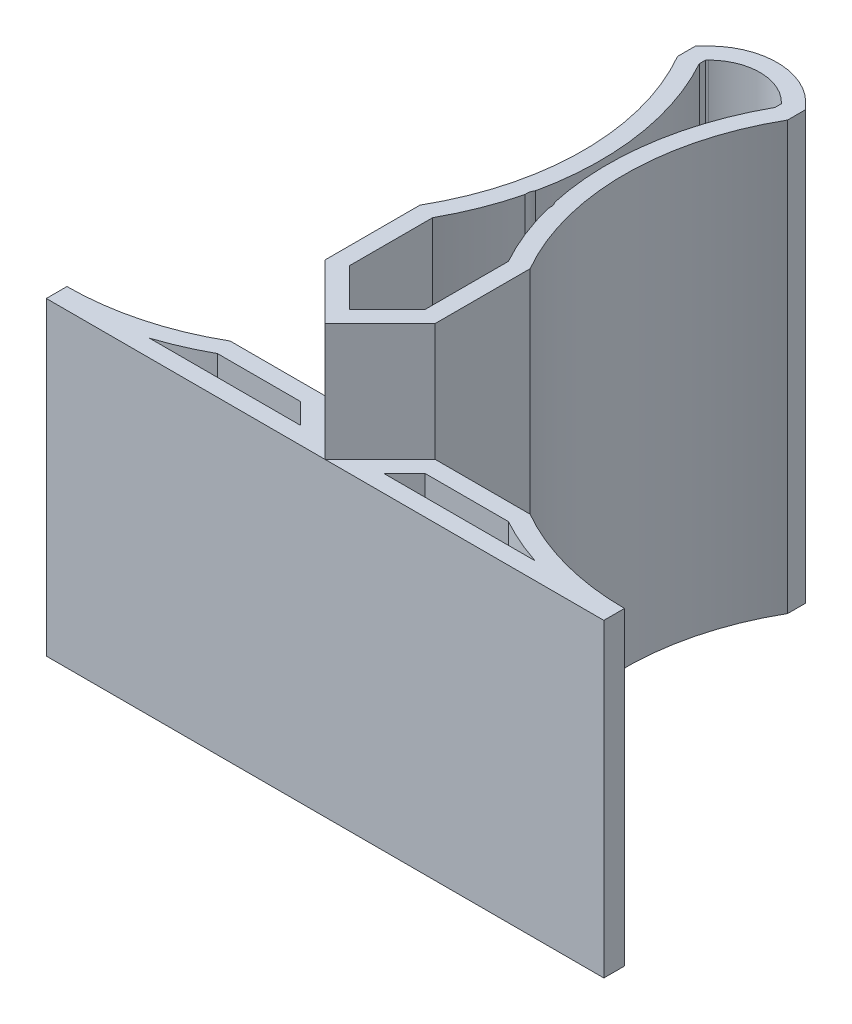
SolidWorks part; units mm, degrees
ref_plane "Front Plane" through (0, 0, 0) normal (0, 0, 1) x (1, 0, 0)
ref_plane "Top Plane" through (0, 0, 0) normal (0, 1, 0) x (1, 0, 0)
ref_plane "Right Plane" through (0, 0, 0) normal (1, 0, 0) x (0, 0, -1)
sketch "Sketch1" plane through (0, 0, 0) normal (0, 1, 0) x (1, 0, 0)
  line L0 (23.7595, 41.275) -> (41.275, 41.275) construction
  line L1 (-41.275, -41.275) -> (-23.7595, -41.275) construction
  line L2 (-41.275, -41.275) -> (-41.275, -23.7595) construction
  line L3 (-41.275, 41.275) -> (-23.7595, 41.275) construction
  line L4 (41.275, -41.275) -> (41.275, -23.7595) construction
  line L5 (-41.275, -41.275) -> (41.275, 41.275) construction
  line L6 (-41.275, 41.275) -> (41.275, -41.275) construction
  line L7 (41.275, 23.7595) -> (41.275, 41.275) construction
  line L8 (-41.275, 23.7595) -> (-41.275, 41.275) construction
  line L9 (23.7595, -41.275) -> (41.275, -41.275) construction
  line L10 (24.7569, 45.085) -> (45.085, 45.085) construction
  line L11 (45.085, 24.7569) -> (45.085, 45.085) construction
  line L12 (45.085, -45.085) -> (45.085, -24.7569) construction
  line L13 (24.7569, -45.085) -> (45.085, -45.085) construction
  line L14 (-45.085, -45.085) -> (-24.7569, -45.085) construction
  line L15 (-45.085, -45.085) -> (-45.085, -24.7569) construction
  line L16 (-45.085, 24.7569) -> (-45.085, 45.085) construction
  line L17 (-45.085, 45.085) -> (-24.7569, 45.085) construction
  line L19 (-51.435, -51.435) -> (51.435, -51.435) construction
  line L20 (-51.435, -51.435) -> (-51.435, 51.435) construction
  line L21 (-51.435, 51.435) -> (51.435, 51.435) construction
  line L22 (51.435, -51.435) -> (51.435, 51.435) construction
  line L23 (-51.435, -51.435) -> (51.435, 51.435) construction
  line L24 (-51.435, 51.435) -> (51.435, -51.435) construction
  arc A1 (-41.275, 23.7595) -> (-41.275, -23.7595) centre (0, 0) ccw construction
  arc A2 (23.7595, 41.275) -> (-23.7595, 41.275) centre (0, 0) ccw construction
  arc A3 (-23.7595, -41.275) -> (23.7595, -41.275) centre (0, 0) ccw construction
  arc A4 (41.275, -23.7595) -> (41.275, 23.7595) centre (0, 0) ccw construction
  arc A5 (45.085, -24.7569) -> (45.085, 24.7569) centre (0, 0) ccw construction
  arc A6 (-24.7569, -45.085) -> (24.7569, -45.085) centre (0, 0) ccw construction
  arc A7 (-45.085, 24.7569) -> (-45.085, -24.7569) centre (0, 0) ccw construction
  arc A8 (24.7569, 45.085) -> (-24.7569, 45.085) centre (0, 0) ccw construction
  point P0 (0, 0)
  dimension "D1" = 82.55
  dimension "D2" = 82.55
  dimension "D3" = 95.25
  dimension "D4" = 3.81
sketch "Sketch2" plane through (0, 0, 0) normal (0, 0, 1) x (1, 0, 0)
  line L0 (0, 48) -> (0, 0) construction
  line L1 (0, 0) -> (0, -9.15) construction
  line L2 (0, 48) -> (0, 69.717) construction
  dimension "Cage height" = 48
  dimension "Plate height" = 21.717
  dimension "D1" = 57.15
  dimension "D2" = 9.15
sketch "Sketch13" plane through (0, 0, 0) normal (0, 1, 0) x (1, 0, 0)
  line L0 (-51.435, -51.435) -> (51.435, -51.435) construction
  line L1 (-41.275, -41.275) -> (-23.7595, -41.275) construction
  line L2 (-41.275, -41.275) -> (-41.275, -23.7595) construction
  line L4 (-51.435, -51.435) -> (0, -51.435)
  line L5 (-41.275, -41.275) -> (-23.7595, -41.275)
  line L6 (-41.275, -41.275) -> (-41.275, -23.7595)
  line L9 (0, -47.625) -> (0, -51.435)
  line L10 (-51.435, 51.435) -> (51.435, -51.435) construction
  line L11 (-41.275, 23.7595) -> (-41.275, 41.275) construction
  line L12 (-51.435, -51.435) -> (-51.435, 51.435) construction
  line L13 (-51.435, 51.435) -> (-41.275, 41.275)
  line L14 (-41.275, 23.7595) -> (-41.275, 41.275)
  line L15 (-51.435, -51.435) -> (-51.435, 51.435)
  arc A0 (-23.7595, -41.275) -> (23.7595, -41.275) centre (0, 0) ccw construction
  arc A2 (-23.7595, -41.275) -> (0, -47.625) centre (0, 0) ccw
  arc A4 (-41.275, 23.7595) -> (-41.275, -23.7595) centre (0, 0) ccw construction
  arc A5 (-41.275, 23.7595) -> (-41.275, -23.7595) centre (0, 0) ccw
extrude "Boss-Extrude2" add sketch "Sketch13" along normal up to vertex (69.717 mm away) and the other way up to vertex (9.15 mm away) up to point (0, 69.717, 0) other way up to point (0, -9.15, 0)
sketch "Sketch15" plane through (0, 69.717, 0) normal (0, 1, 0) x (1, 0, 0)
  line L0 (0, 0) -> (-51.435, -51.435)
  line L1 (-51.435, -51.435) -> (0, -51.435)
  line L2 (0, -51.435) -> (0, 0)
  line L3 (-51.435, -51.435) -> (51.435, -51.435) construction
extrude "Cut-Extrude2" cut sketch "Sketch15" against normal up to vertex (21.717 mm away) up to point (0, 48, 0)
mirror "Mirror1" about plane through (-51.435, 69.717, 51.435) normal (1, 0, 0) of "Boss-Extrude2", "Cut-Extrude2"
sketch "Sketch16" plane through (0, -9.15, 0) normal (0, -1, 0) x (1, 0, 0)
  line L0 (-51.435, 51.435) -> (-51.435, -51.435) construction
  line L1 (-102.87, 51.435) -> (0, 51.435) construction
  line L2 (-51.435, 51.435) -> (-51.435, -51.435) construction
  circle A0 centre (-70.485, 46.355) radius 1.85
  circle A1 centre (-51.435, 25.4) radius 1.85
  circle A3 centre (-32.385, 46.355) radius 1.85
  circle A5 centre (-51.435, -25.4) radius 1.85
  dimension "D1" = 3.7
  dimension "D2" = 19.05
  dimension "D3" = 5.08
  dimension "D4" = 25.4
  dimension "D6" = 25.4
extrude "Cut-Extrude3" cut sketch "Sketch16" against normal blind 31.75
sketch "Sketch17" plane through (0, 69.717, 0) normal (0, 1, 0) x (1, 0, 0)
  line L0 (7.0944, 7.0944) -> (-7.0944, -7.0944)
  line L1 (7.0944, 7.0944) -> (-44.3406, 58.5294)
  line L2 (-7.0944, -7.0944) -> (-51.435, 37.2462)
  line L3 (-44.3406, 58.5294) -> (-51.435, 51.435)
  line L4 (-41.275, -41.275) -> (41.275, 41.275) construction
  line L5 (-61.595, 41.275) -> (-51.435, 51.435) construction
  line L6 (-51.435, -51.435) -> (-51.435, 51.435) construction
  line L7 (-51.435, 7.7321) -> (-51.435, 82.5591) construction
  line L8 (-95.7756, -7.0944) -> (-51.435, 37.2462)
  line L9 (-58.5294, 58.5294) -> (-51.435, 51.435)
  line L10 (-109.9644, 7.0944) -> (-58.5294, 58.5294)
  line L11 (-109.9644, 7.0944) -> (-95.7756, -7.0944)
  dimension "D1" = 20.066
extrude "Cut-Extrude4" cut sketch "Sketch17" against normal through all
fillet "Fillet2" radius 12.7 1 edges at (-51.435, 30.2835, -37.2462)
sketch "Sketch18" plane through (0, 69.717, 0) normal (0, 1, 0) x (1, 0, 0)
  line L19 (-58.42, -24.5934) -> (-58.42, -39.9599)
  line L20 (-58.42, -39.9599) -> (-51.435, -46.9449)
  line L21 (-51.435, -46.9449) -> (-44.45, -39.9599)
  line L22 (-44.45, -39.9599) -> (-44.45, -24.5934)
  line L27 (-58.42, -24.5934) -> (-58.42, -39.9599)
  line L28 (-58.42, -39.9599) -> (-51.435, -46.9449)
  line L29 (-51.435, -46.9449) -> (-44.45, -39.9599)
  line L30 (-44.45, -39.9599) -> (-44.45, -24.5934)
  line L32 (-62.9101, -44.45) -> (-78.2766, -44.45)
  line L33 (-87.0077, -48.26) -> (-59.1001, -48.26)
  line L34 (-59.1001, -48.26) -> (-62.9101, -44.45)
  line L35 (-62.9101, -44.45) -> (-78.2766, -44.45)
  line L36 (-87.0077, -48.26) -> (-59.1001, -48.26)
  line L37 (-59.1001, -48.26) -> (-62.9101, -44.45)
  line L42 (-24.5934, -44.45) -> (-39.9599, -44.45)
  line L43 (-39.9599, -44.45) -> (-43.7699, -48.26)
  line L44 (-43.7699, -48.26) -> (-15.8623, -48.26)
  line L45 (-24.5934, -44.45) -> (-39.9599, -44.45)
  line L46 (-39.9599, -44.45) -> (-43.7699, -48.26)
  line L47 (-43.7699, -48.26) -> (-15.8623, -48.26)
  line L48 (-44.45, 25.7711) -> (-44.6998, 26.0209)
  line L49 (-44.45, 25.7711) -> (-44.6998, 26.0209)
  line L50 (-58.1702, 26.0209) -> (-58.42, 25.7711)
  line L51 (-58.1702, 26.0209) -> (-58.42, 25.7711)
  line L52 (-58.42, 25.7711) -> (-58.42, 24.5934)
  line L53 (-58.42, 25.7711) -> (-58.42, 24.5934)
  line L54 (-44.45, 24.5934) -> (-44.45, 25.7711)
  line L55 (-44.45, 24.5934) -> (-44.45, 25.7711)
  arc A5 (-87.0077, -48.26) -> (-78.2766, -44.45) centre (-102.87, 0) ccw
  arc A6 (-44.6998, 26.0209) -> (-58.1702, 26.0209) centre (-51.435, 19.2857) ccw
  arc A7 (-58.42, -24.5934) -> (-58.42, 24.5934) centre (-102.87, 0) ccw
  arc A8 (-44.45, 24.5934) -> (-44.45, -24.5934) centre (0, 0) ccw
  arc A9 (-44.6998, 26.0209) -> (-58.1702, 26.0209) centre (-51.435, 19.2857) ccw
  arc A10 (-58.42, -24.5934) -> (-58.42, 24.5934) centre (-102.87, 0) ccw
  arc A11 (-44.45, 24.5934) -> (-44.45, -24.5934) centre (0, 0) ccw
  arc A12 (-87.0077, -48.26) -> (-78.2766, -44.45) centre (-102.87, 0) ccw
  arc A14 (-24.5934, -44.45) -> (-15.8623, -48.26) centre (0, 0) ccw
  arc A15 (-24.5934, -44.45) -> (-15.8623, -48.26) centre (0, 0) ccw
  dimension "D1" = 3.175
  dimension "D2" = 3.175
  dimension "D3" = 3.175
extrude "Cut-Extrude5" cut sketch "Sketch18" against normal up to surface (47.117 mm away) up to face at (-51.435, 22.6, -27.25)
sketch "Sketch20" plane through (0, 22.6, 0) normal (0, 1, 0) x (1, 0, 0)
  line L0 (-58.42, -31.75) -> (-44.45, -31.75)
  line L2 (-47.0929, 19.05) -> (-55.7771, 19.05)
  line L3 (-55.7771, -19.05) -> (-47.0929, -19.05)
  line L12 (-58.42, -24.5934) -> (-58.42, -39.9599)
  line L13 (-58.42, -39.9599) -> (-51.435, -46.9449)
  line L14 (-51.435, -46.9449) -> (-44.45, -39.9599)
  line L15 (-44.45, -39.9599) -> (-44.45, -24.5934)
  line L20 (-58.42, -31.75) -> (-58.42, -39.9599)
  line L21 (-58.42, -39.9599) -> (-51.435, -46.9449)
  line L22 (-51.435, -46.9449) -> (-44.45, -39.9599)
  line L23 (-44.45, -39.9599) -> (-44.45, -31.75)
  line L25 (-44.45, 24.5934) -> (-44.45, 25.7711)
  line L26 (-44.45, 25.7711) -> (-44.6998, 26.0209)
  line L27 (-58.1702, 26.0209) -> (-58.42, 25.7711)
  line L28 (-58.42, 25.7711) -> (-58.42, 24.5934)
  circle A0 centre (-51.435, -25.4) radius 1.85 construction
  circle A1 centre (-51.435, 25.4) radius 1.85 construction
  arc A4 (-58.42, -24.5934) -> (-58.42, 24.5934) centre (-102.87, 0) ccw
  arc A5 (-44.45, 24.5934) -> (-44.45, -24.5934) centre (0, 0) ccw
  arc A7 (-55.7771, -19.05) -> (-55.7771, 19.05) centre (-102.87, 0) ccw
  arc A8 (-47.0929, 19.05) -> (-47.0929, -19.05) centre (0, 0) ccw
  arc A11 (-44.6998, 26.0209) -> (-58.1702, 26.0209) centre (-51.435, 19.2857) ccw
  dimension "D2" = 6.35
  dimension "D5" = 6.35
  dimension "D3" = 6.35
  dimension "D1" = 0
extrude "Cut-Extrude6" cut sketch "Sketch20" against normal through all
sketch "Sketch21" plane through (0, -9.15, 0) normal (0, 1, 0) x (1, 0, 0)
  circle A0 centre (-51.435, 25.4) radius 1.85 construction
  circle A1 centre (-51.435, -25.4) radius 1.85 construction
  circle A2 centre (-32.385, -46.355) radius 1.85 construction
  circle A3 centre (-70.485, -46.355) radius 1.85 construction
  circle A4 centre (-51.435, 25.4) radius 1.85 construction
  circle A5 centre (-51.435, -25.4) radius 1.85 construction
  circle A6 centre (-32.385, -46.355) radius 1.85 construction
  circle A7 centre (-70.485, -46.355) radius 1.85 construction
sketch "Sketch22" plane through (0, 0, 0) normal (0, 1, 0) x (1, 0, 0)
  line L0 (-51.435, -51.435) -> (-51.435, 51.435) construction
  line L1 (-51.435, 51.435) -> (51.435, 51.435) construction
  circle A0 centre (-51.435, -12.065) radius 2.2
  dimension "D1" = 4.4
  dimension "D2" = 63.5
extrude "Cut-Extrude7" cut sketch "Sketch22" against normal through all both and the other way through all
equation "\"tightTol\"= 0.005in"
equation "\"normTol\"= 0.01in"
equation "\"looseTol\"= 0.02in"
equation "\"Cage height@Sketch2\"=48mm"
equation "\"Plate height@Sketch2\"=0.875in - \"looseTol\""
equation "\"D1@Sketch16\"=3.7mm"
equation "\"D1@Sketch17\"=0.75in+2*\"looseTol\""
equation "\"D1@Sketch22\"=4.4mm"
